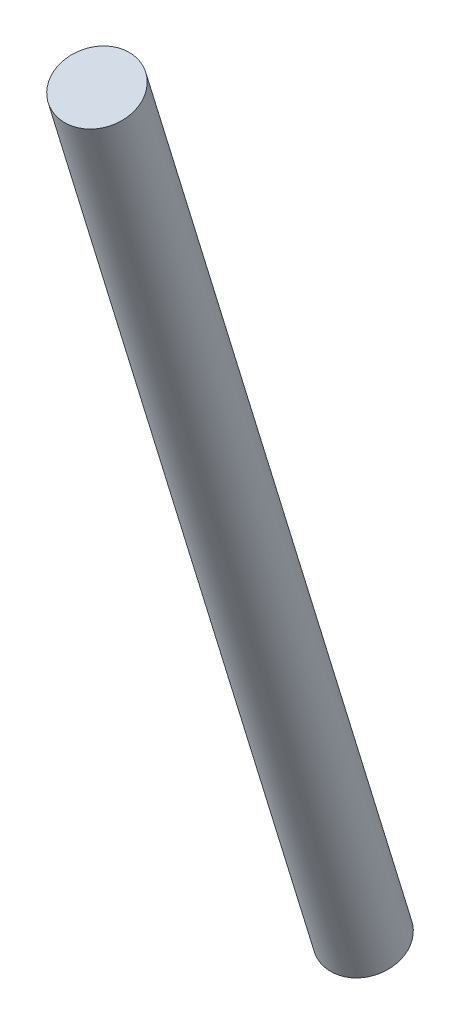
SolidWorks part; units mm, degrees
ref_plane "Front Plane" through (0, 0, 0) normal (0, 0, 1) x (1, 0, 0)
ref_plane "Top Plane" through (0, 0, 0) normal (0, 1, 0) x (1, 0, 0)
ref_plane "Right Plane" through (0, 0, 0) normal (1, 0, 0) x (0, 0, -1)
sketch3d "3DSketch1"
  line L0 (208.7285, 112.0637, 175.5826) -> (164.2785, 112.0637, 175.5826) construction
  line L2 (208.7285, 112.0637, 175.5826) -> (-19.8715, 112.0637, 175.5826) construction
  line L3 (164.2785, 106.0568, 191.6408) -> (164.2785, 118.0705, 159.5243) construction
  line L4 (234.1285, 568.2379, 346.2223) -> (208.7285, 568.2379, 346.2223) construction
  line L5 (164.2785, 112.0637, 175.5826) -> (208.7285, 568.2379, 346.2223)
  circle A0 centre (234.1285, 568.2379, 346.2223) radius 15.875 construction
  point P10 (218.2535, 568.2379, 346.2223)
  dimension "D1" = 25.4
sweep "Sweep1" add path "3DSketch1" circular profile diameter 34.29 parameters "D3"=34.29
